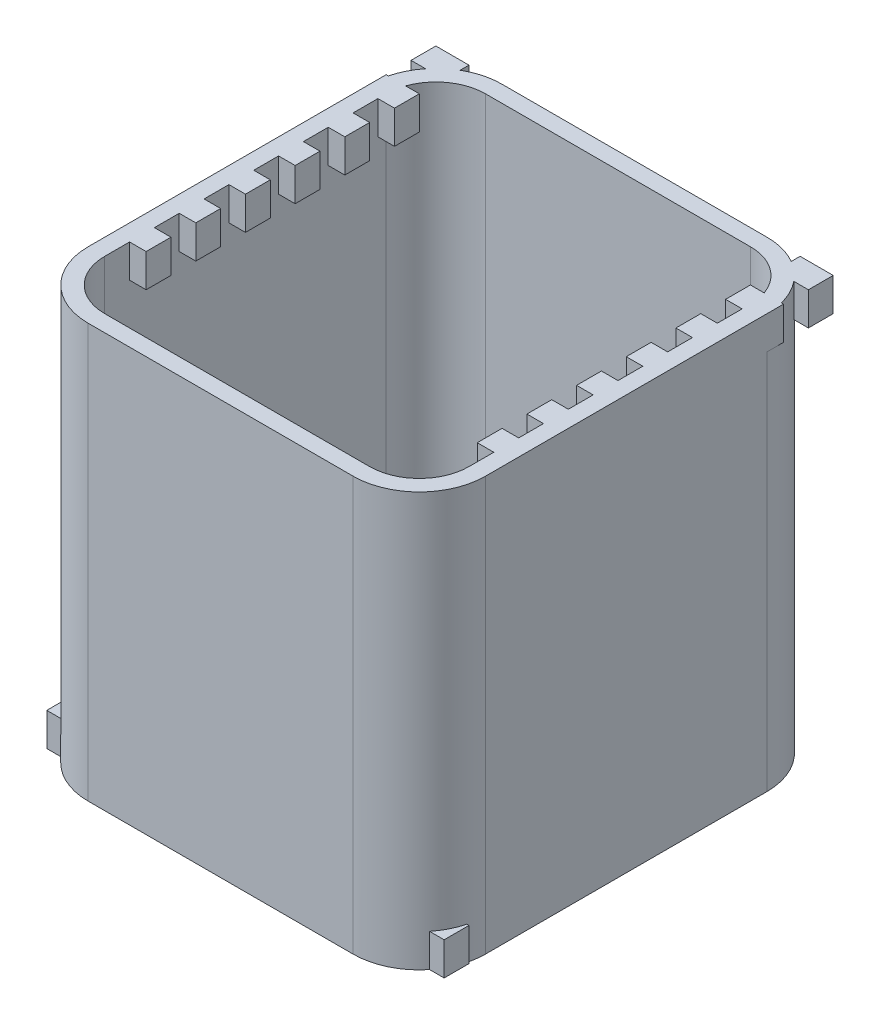
SolidWorks part; units mm, degrees
ref_plane "Front Plane" through (0, 0, 0) normal (0, 0, 1) x (1, 0, 0)
ref_plane "Top Plane" through (0, 0, 0) normal (0, 1, 0) x (1, 0, 0)
ref_plane "Right Plane" through (0, 0, 0) normal (1, 0, 0) x (0, 0, -1)
sketch "Sketch1" plane through (0, 0, 0) normal (0, 1, 0) x (1, 0, 0)
  line L0 (356.5379, 539.6819) -> (1600.9879, 539.6819) construction
  line L1 (-10, 30) -> (-10, 200)
  line L2 (30, 0) -> (190, 0)
  line L3 (0, 30) -> (0, 200)
  line L4 (30, 230) -> (190, 230)
  line L5 (220, 30) -> (220, 200)
  line L6 (30, 240) -> (190, 240)
  line L7 (230, 30) -> (230, 200)
  line L8 (30, -10) -> (190, -10)
  arc A0 (30, 230) -> (0, 200) centre (30, 200) ccw
  arc A1 (190, 230) -> (220, 200) centre (190, 200) cw
  arc A2 (220, 30) -> (190, 0) centre (190, 30) cw
  arc A3 (0, 30) -> (30, 0) centre (30, 30) ccw
  arc A4 (30, 240) -> (-10, 200) centre (30, 200) ccw
  arc A5 (190, 240) -> (230, 200) centre (190, 200) cw
  arc A6 (230, 30) -> (190, -10) centre (190, 30) cw
  arc A7 (-10, 30) -> (30, -10) centre (30, 30) ccw
  point P13 (220, 0)
  point P16 (0, 0)
  dimension "D3" = 30
  dimension "D1" = 230
  dimension "D2" = 220
  dimension "D4" = 10
extrude "Boss-Extrude1" add sketch "Sketch1" along normal blind 250
sketch "Sketch3" plane through (-10, 0, 0) normal (-1, 0, 0) x (0, 0, 1)
  line L1 (-200, 0) -> (-185, 0)
  line L2 (-200, 0) -> (-200, 20)
  line L3 (-200, 20) -> (-185, 20)
  line L4 (-185, 0) -> (-185, 20)
  line L5 (-185, 0) -> (-185, 20)
  line L6 (-185, 0) -> (-170, 0)
  line L7 (-170, 0) -> (-170, 20)
  line L8 (-185, 20) -> (-170, 20)
  line L9 (-170, 0) -> (-170, 20)
  line L10 (-170, 0) -> (-155, 0)
  line L11 (-155, 0) -> (-155, 20)
  line L12 (-170, 20) -> (-155, 20)
  line L13 (-155, 0) -> (-155, 20)
  line L14 (-155, 0) -> (-140, 0)
  line L15 (-140, 0) -> (-140, 20)
  line L16 (-155, 20) -> (-140, 20)
  line L17 (-140, 0) -> (-140, 20)
  line L18 (-140, 0) -> (-125, 0)
  line L19 (-125, 0) -> (-125, 20)
  line L20 (-140, 20) -> (-125, 20)
  line L21 (-125, 0) -> (-125, 20)
  line L22 (-125, 0) -> (-110, 0)
  line L23 (-110, 0) -> (-110, 20)
  line L24 (-125, 20) -> (-110, 20)
  line L25 (-110, 0) -> (-110, 20)
  line L26 (-110, 0) -> (-95, 0)
  line L27 (-95, 0) -> (-95, 20)
  line L28 (-110, 20) -> (-95, 20)
  line L29 (-95, 0) -> (-95, 20)
  line L30 (-95, 0) -> (-80, 0)
  line L31 (-80, 0) -> (-80, 20)
  line L32 (-95, 20) -> (-80, 20)
  line L33 (-80, 0) -> (-80, 20)
  line L34 (-80, 0) -> (-65, 0)
  line L35 (-65, 0) -> (-65, 20)
  line L36 (-80, 20) -> (-65, 20)
  line L37 (-65, 0) -> (-65, 20)
  line L38 (-65, 0) -> (-50, 0)
  line L39 (-50, 0) -> (-50, 20)
  line L40 (-65, 20) -> (-50, 20)
  line L41 (-50, 0) -> (-50, 20)
  line L42 (-50, 0) -> (-35, 0)
  line L43 (-35, 0) -> (-35, 20)
  line L44 (-50, 20) -> (-35, 20)
  line L45 (-35, 0) -> (-35, 20)
  line L46 (-35, 0) -> (-20, 0)
  line L47 (-20, 0) -> (-20, 20)
  line L48 (-35, 20) -> (-20, 20)
  line L49 (-20, 0) -> (-20, 20)
  line L50 (-20, 0) -> (-5, 0)
  line L51 (-5, 0) -> (-5, 20)
  line L52 (-20, 20) -> (-5, 20)
  line L53 (-5, 0) -> (-5, 20)
  line L54 (-5, 0) -> (10, 0)
  line L55 (10, 0) -> (10, 20)
  line L56 (-5, 20) -> (10, 20)
  line L57 (10, 0) -> (10, 20)
  line L58 (10, 0) -> (25, 0)
  line L59 (25, 0) -> (25, 20)
  line L60 (10, 20) -> (25, 20)
  line L61 (25, 0) -> (25, 20)
  line L62 (25, 0) -> (40, 0)
  line L63 (40, 0) -> (40, 20)
  line L64 (25, 20) -> (40, 20)
  line M3 (-200, 0) -> (-30, 0)
  line M5 (-30, 250) -> (-200, 250)
  line M6 (-200, 250) -> (-200, 0)
  dimension "D1" = 15
  dimension "D3" = 20
  dimension "D2" = 16
extrude "Boss-Extrude2" add sketch "Sketch3" against normal blind 20 contours L4 M3 M5 M6 | L11 L7 M3 M5 | L19 L15 M3 M5 | L35 L31 M3 M5 | L43 L39 M3 M5 | L51 L47 M3 M5 | L27 L28 L25 L26 region at (-10, 10, -192.5) region at (-10, 10, -162.5) region at (-10, 10, -132.5) region at (-10, 10, -72.5) region at (-10, 10, -42.5) region at (-10, 10, -12.5)
sketch "Sketch4" plane through (230, 0, 0) normal (1, 0, 0) x (0, 0, -1)
  line L1 (200, 0) -> (185, 0)
  line L2 (200, 0) -> (200, 20)
  line L3 (200, 20) -> (185, 20)
  line L4 (185, 0) -> (185, 20)
  line L5 (185, 0) -> (185, 20)
  line L6 (185, 0) -> (170, 0)
  line L7 (170, 0) -> (170, 20)
  line L8 (185, 20) -> (170, 20)
  line L9 (170, 0) -> (170, 20)
  line L10 (170, 0) -> (155, 0)
  line L11 (155, 0) -> (155, 20)
  line L12 (170, 20) -> (155, 20)
  line L13 (155, 0) -> (155, 20)
  line L14 (155, 0) -> (140, 0)
  line L15 (140, 0) -> (140, 20)
  line L16 (155, 20) -> (140, 20)
  line L17 (140, 0) -> (140, 20)
  line L18 (140, 0) -> (125, 0)
  line L19 (125, 0) -> (125, 20)
  line L20 (140, 20) -> (125, 20)
  line L21 (125, 0) -> (125, 20)
  line L22 (125, 0) -> (110, 0)
  line L23 (110, 0) -> (110, 20)
  line L24 (125, 20) -> (110, 20)
  line L25 (110, 0) -> (110, 20)
  line L26 (110, 0) -> (95, 0)
  line L27 (95, 0) -> (95, 20)
  line L28 (110, 20) -> (95, 20)
  line L29 (95, 0) -> (95, 20)
  line L30 (95, 0) -> (80, 0)
  line L31 (80, 0) -> (80, 20)
  line L32 (95, 20) -> (80, 20)
  line L33 (80, 0) -> (80, 20)
  line L34 (80, 0) -> (65, 0)
  line L35 (65, 0) -> (65, 20)
  line L36 (80, 20) -> (65, 20)
  line L37 (65, 0) -> (65, 20)
  line L38 (65, 0) -> (50, 0)
  line L39 (50, 0) -> (50, 20)
  line L40 (65, 20) -> (50, 20)
  line L41 (50, 0) -> (50, 20)
  line L42 (50, 0) -> (35, 0)
  line L43 (35, 0) -> (35, 20)
  line L44 (50, 20) -> (35, 20)
  line L45 (35, 0) -> (35, 20)
  line L46 (35, 0) -> (20, 0)
  line L47 (20, 0) -> (20, 20)
  line L48 (35, 20) -> (20, 20)
  line L49 (20, 0) -> (20, 20)
  line L50 (20, 0) -> (5, 0)
  line L51 (5, 0) -> (5, 20)
  line L52 (20, 20) -> (5, 20)
  line L53 (5, 0) -> (5, 20)
  line L54 (5, 0) -> (-10, 0)
  line L55 (-10, 0) -> (-10, 20)
  line L56 (5, 20) -> (-10, 20)
  line L57 (-10, 0) -> (-10, 20)
  line L58 (-10, 0) -> (-25, 0)
  line L59 (-25, 0) -> (-25, 20)
  line L60 (-10, 20) -> (-25, 20)
  line L61 (-25, 0) -> (-25, 20)
  line L62 (-25, 0) -> (-40, 0)
  line L63 (-40, 0) -> (-40, 20)
  line L64 (-25, 20) -> (-40, 20)
  line M5 (30, 0) -> (200, 0)
  line M6 (200, 0) -> (200, 250)
  line M7 (200, 250) -> (30, 250)
  dimension "D1" = 15
  dimension "D3" = 20
  dimension "D2" = 16
extrude "Boss-Extrude3" add sketch "Sketch4" against normal blind 20 contours L4 M5 M6 M7 | L11 L7 M5 M7 | L27 L23 M5 M7 | L35 L31 M5 M7 | L43 L39 M5 M7 | L51 L47 M5 M7 | L18 L19 L20 L17 region at (230, 10, -192.5) region at (230, 10, -162.5) region at (230, 10, -102.5) region at (230, 10, -72.5) region at (230, 10, -42.5) region at (230, 10, -12.5)
sketch "Sketch8" plane through (-10, 0, 0) normal (1, 0, 0) x (0, 0, -1)
  line L0 (45, 250) -> (45, 230)
  line L1 (30, 250) -> (45, 250)
  line L2 (30, 250) -> (30, 230)
  line L3 (30, 230) -> (45, 230)
  line L4 (45, 250) -> (45, 230)
  line L5 (45, 250) -> (60, 250)
  line L6 (60, 250) -> (60, 230)
  line L7 (45, 230) -> (60, 230)
  line L8 (60, 250) -> (60, 230)
  line L9 (60, 250) -> (75, 250)
  line L10 (75, 250) -> (75, 230)
  line L11 (60, 230) -> (75, 230)
  line L12 (75, 250) -> (75, 230)
  line L13 (75, 250) -> (90, 250)
  line L14 (90, 250) -> (90, 230)
  line L15 (75, 230) -> (90, 230)
  line L16 (90, 250) -> (90, 230)
  line L17 (90, 250) -> (105, 250)
  line L18 (105, 250) -> (105, 230)
  line L19 (90, 230) -> (105, 230)
  line L20 (105, 250) -> (105, 230)
  line L21 (105, 250) -> (120, 250)
  line L22 (120, 250) -> (120, 230)
  line L23 (105, 230) -> (120, 230)
  line L24 (120, 250) -> (120, 230)
  line L25 (120, 250) -> (135, 250)
  line L26 (135, 250) -> (135, 230)
  line L27 (120, 230) -> (135, 230)
  line L28 (135, 250) -> (135, 230)
  line L29 (135, 250) -> (150, 250)
  line L30 (150, 250) -> (150, 230)
  line L31 (135, 230) -> (150, 230)
  line L32 (150, 250) -> (150, 230)
  line L33 (150, 250) -> (165, 250)
  line L34 (165, 250) -> (165, 230)
  line L35 (150, 230) -> (165, 230)
  line L36 (165, 250) -> (165, 230)
  line L37 (165, 250) -> (180, 250)
  line L38 (180, 250) -> (180, 230)
  line L39 (165, 230) -> (180, 230)
  line L40 (180, 250) -> (180, 230)
  line L41 (180, 250) -> (195, 250)
  line L42 (195, 250) -> (195, 230)
  line L43 (180, 230) -> (195, 230)
  line L44 (195, 250) -> (195, 230)
  line L45 (195, 250) -> (210, 250)
  line L46 (210, 250) -> (210, 230)
  line L47 (195, 230) -> (210, 230)
  line L48 (210, 250) -> (210, 230)
  line L49 (210, 250) -> (225, 250)
  line L50 (225, 250) -> (225, 230)
  line L51 (210, 230) -> (225, 230)
  line L52 (225, 250) -> (225, 230)
  line L53 (225, 250) -> (240, 250)
  line L54 (240, 250) -> (240, 230)
  line L55 (225, 230) -> (240, 230)
  line L56 (240, 250) -> (240, 230)
  line L57 (240, 250) -> (255, 250)
  line L58 (255, 250) -> (255, 230)
  line L59 (240, 230) -> (255, 230)
  line L60 (255, 250) -> (255, 230)
  line L61 (255, 250) -> (270, 250)
  line L62 (270, 250) -> (270, 230)
  line L63 (255, 230) -> (270, 230)
  line L64 (30, 250) -> (45, 250) construction
  point P5 (37.5, 230)
  line M45 (30, 250) -> (200, 250)
  dimension "D1" = 15
  dimension "D2" = 20
  dimension "D4" = 15
  dimension "D3" = 16
extrude "Boss-Extrude5" add sketch "Sketch8" along normal blind 20 contours L39 L34 L38 M45 | L31 L26 L30 M45 | L23 L18 L22 M45 | L7 L0 L6 M45 | L54 L55 L52 L53 | L14 L15 L12 L13 | L44 L47 L46 L45 region at (-10, 240, -52.5) region at (-10, 240, -112.5) region at (-10, 240, -142.5) region at (-10, 240, -172.5)
sketch "Sketch9" plane through (230, 0, 0) normal (1, 0, 0) x (0, 0, -1)
  line L0 (45, 250) -> (45, 230)
  line L1 (30, 250) -> (45, 250)
  line L2 (30, 250) -> (30, 230)
  line L3 (30, 230) -> (45, 230)
  line L4 (45, 250) -> (45, 230)
  line L5 (45, 250) -> (60, 250)
  line L6 (60, 250) -> (60, 230)
  line L7 (45, 230) -> (60, 230)
  line L8 (60, 250) -> (60, 230)
  line L9 (60, 250) -> (75, 250)
  line L10 (75, 250) -> (75, 230)
  line L11 (60, 230) -> (75, 230)
  line L12 (75, 250) -> (75, 230)
  line L13 (75, 250) -> (90, 250)
  line L14 (90, 250) -> (90, 230)
  line L15 (75, 230) -> (90, 230)
  line L16 (90, 250) -> (90, 230)
  line L17 (90, 250) -> (105, 250)
  line L18 (105, 250) -> (105, 230)
  line L19 (90, 230) -> (105, 230)
  line L20 (105, 250) -> (105, 230)
  line L21 (105, 250) -> (120, 250)
  line L22 (120, 250) -> (120, 230)
  line L23 (105, 230) -> (120, 230)
  line L24 (120, 250) -> (120, 230)
  line L25 (120, 250) -> (135, 250)
  line L26 (135, 250) -> (135, 230)
  line L27 (120, 230) -> (135, 230)
  line L28 (135, 250) -> (135, 230)
  line L29 (135, 250) -> (150, 250)
  line L30 (150, 250) -> (150, 230)
  line L31 (135, 230) -> (150, 230)
  line L32 (150, 250) -> (150, 230)
  line L33 (150, 250) -> (165, 250)
  line L34 (165, 250) -> (165, 230)
  line L35 (150, 230) -> (165, 230)
  line L36 (165, 250) -> (165, 230)
  line L37 (165, 250) -> (180, 250)
  line L38 (180, 250) -> (180, 230)
  line L39 (165, 230) -> (180, 230)
  line L40 (180, 250) -> (180, 230)
  line L41 (180, 250) -> (195, 250)
  line L42 (195, 250) -> (195, 230)
  line L43 (180, 230) -> (195, 230)
  line L44 (195, 250) -> (195, 230)
  line L45 (195, 250) -> (210, 250)
  line L46 (210, 250) -> (210, 230)
  line L47 (195, 230) -> (210, 230)
  line L48 (210, 250) -> (210, 230)
  line L49 (210, 250) -> (225, 250)
  line L50 (225, 250) -> (225, 230)
  line L51 (210, 230) -> (225, 230)
  line L52 (225, 250) -> (225, 230)
  line L53 (225, 250) -> (240, 250)
  line L54 (240, 250) -> (240, 230)
  line L55 (225, 230) -> (240, 230)
  line L56 (240, 250) -> (240, 230)
  line L57 (240, 250) -> (255, 250)
  line L58 (255, 250) -> (255, 230)
  line L59 (240, 230) -> (255, 230)
  line L60 (255, 250) -> (255, 230)
  line L61 (255, 250) -> (270, 250)
  line L62 (270, 250) -> (270, 230)
  line L63 (255, 230) -> (270, 230)
  line L64 (30, 250) -> (45, 250) construction
  line M15 (200, 250) -> (30, 250)
  dimension "D1" = 20
  dimension "D2" = 15
  dimension "D4" = 15
  dimension "D3" = 16
extrude "Boss-Extrude6" add sketch "Sketch9" against normal blind 20 contours L10 L15 L14 M15 | L26 L31 L30 M15 | L34 L39 L38 M15 | L0 L7 L6 L5 | L23 L22 L21 L20 | L45 L46 L47 L44 | L52 L55 L54 L53 region at (230, 240, -82.5) region at (230, 240, -142.5) region at (230, 240, -172.5)
